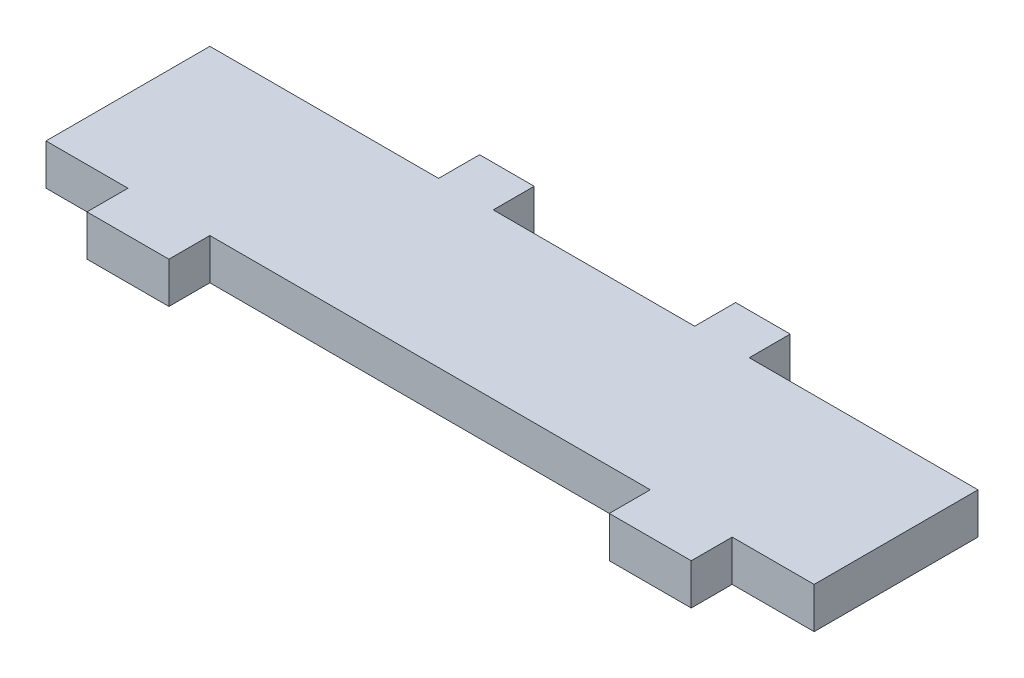
SolidWorks part; units mm, degrees
ref_plane "Front Plane" through (0, 0, 0) normal (0, 0, 1) x (1, 0, 0)
ref_plane "Top Plane" through (0, 0, 0) normal (0, 1, 0) x (1, 0, 0)
ref_plane "Right Plane" through (0, 0, 0) normal (1, 0, 0) x (0, 0, -1)
sketch "Sketch1" plane through (0, 0, 0) normal (0, 1, 0) x (1, 0, 0)
  line L1 (-56.25, -12) -> (56.25, -12)
  line L2 (-56.25, -12) -> (-56.25, 12)
  line L3 (-56.25, 12) -> (56.25, 12)
  line L4 (56.25, -12) -> (56.25, 12)
  line L5 (-56.25, -12) -> (56.25, 12) construction
  line L6 (-56.25, 12) -> (56.25, -12) construction
  point P0 (0, 0)
  dimension "D1" = 112.5
  dimension "D2" = 24
extrude "Boss-Extrude1" add sketch "Sketch1" along normal blind 6
sketch "Sketch2" plane through (0, 0, -12) normal (0, 0, -1) x (-1, 0, 0)
  line L0 (-56.25, 0) -> (56.25, 0) construction
  line L1 (22.75, 0) -> (14.75, 0)
  line L2 (22.75, 0) -> (22.75, 6)
  line L3 (22.75, 6) -> (14.75, 6)
  line L4 (14.75, 0) -> (14.75, 6)
  line L5 (-56.25, 6) -> (56.25, 6) construction
  line L6 (-14.75, 0) -> (-14.75, 6) construction
  line L7 (-14.75, 6) -> (-22.75, 6)
  line L8 (-14.75, 6) -> (-14.75, 0)
  line L9 (-14.75, 0) -> (-22.75, 0)
  line L10 (-22.75, 6) -> (-22.75, 0)
  line L11 (-22.75, 0) -> (-22.75, 6) construction
  line L12 (14.75, 0) -> (-14.75, 0)
  point P3 (22.3863, 0)
  point P12 (14.4526, 0)
  point P24 (0, 0)
  line M7 (-56.25, 0) -> (56.25, 0)
  line M9 (56.25, 6) -> (-56.25, 6)
extrude "Boss-Extrude2" add sketch "Sketch2" along normal blind 6 contours L10 L8 M9 M7 | L4 L2 M7 M9 region at (-18.75, 3, -12) region at (18.75, 3, -12)
sketch "Sketch3" plane through (0, 0, 12) normal (0, 0, 1) x (1, 0, 0)
  line L0 (-32.25, 0) -> (32.25, 0)
  line L1 (-56.25, 0) -> (56.25, 0) construction
  line L2 (32.25, 0) -> (32.25, 6) construction
  line L3 (-56.25, 6) -> (56.25, 6) construction
  line L4 (32.25, 0) -> (44.25, 0)
  line L5 (32.25, 0) -> (32.25, 6)
  line L6 (32.25, 6) -> (44.25, 6)
  line L7 (44.25, 0) -> (44.25, 6)
  line L8 (44.25, 0) -> (44.25, 6) construction
  line L10 (-32.25, 0) -> (-44.25, 0)
  line L11 (-32.25, 0) -> (-32.25, 6)
  line L12 (-32.25, 6) -> (-44.25, 6)
  line L13 (-44.25, 0) -> (-44.25, 6)
  point P7 (0, 0)
  line M6 (-56.25, 0) -> (56.25, 0)
  line M8 (56.25, 6) -> (-56.25, 6)
extrude "Boss-Extrude3" add sketch "Sketch3" along normal blind 6 contours L13 L11 M6 M8 | L7 L5 M6 M8 region at (-38.25, 3, 12) region at (38.25, 3, 12)
